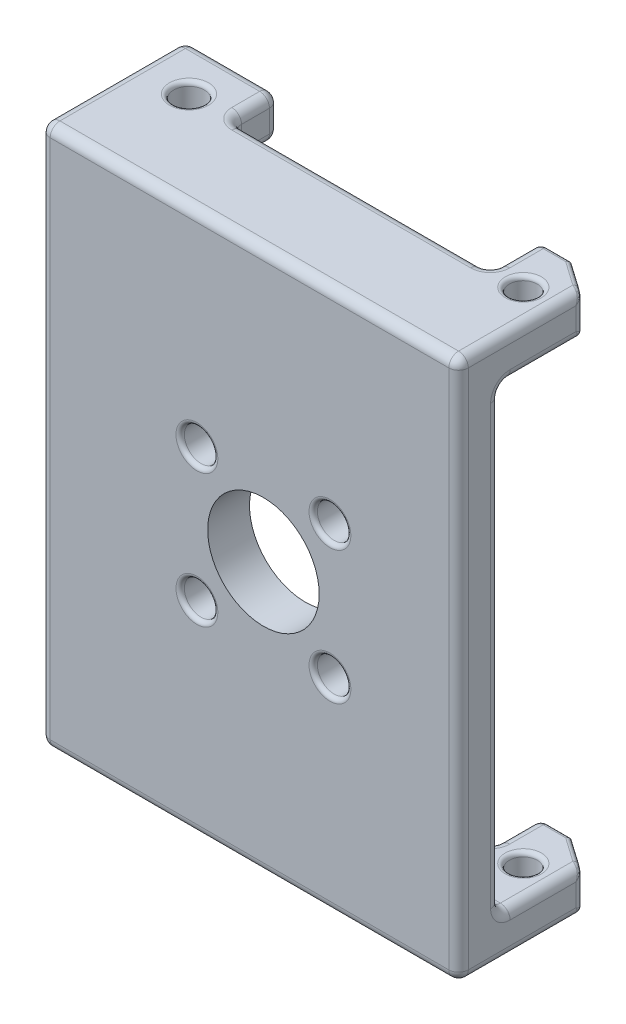
SolidWorks part; units mm, degrees
ref_plane "Front Plane" through (0, 0, 0) normal (0, 0, 1) x (1, 0, 0)
ref_plane "Top Plane" through (0, 0, 0) normal (0, 1, 0) x (1, 0, 0)
ref_plane "Right Plane" through (0, 0, 0) normal (1, 0, 0) x (0, 0, -1)
sketch "Sketch1" plane through (0, 0, 0) normal (0, 0, 1) x (1, 0, 0)
  line L1 (-14, -19.4) -> (14, -19.4)
  line L2 (-14, -19.4) -> (-14, 19.4)
  line L3 (-14, 19.4) -> (14, 19.4)
  line L4 (14, -19.4) -> (14, 19.4)
  line L5 (-14, -19.4) -> (14, 19.4) construction
  line L6 (-14, 19.4) -> (14, -19.4) construction
  circle A0 centre (0, 0) radius 4
  circle A1 centre (4.773, 4.773) radius 1.2
  circle A2 centre (4.773, -4.773) radius 1.2
  circle A3 centre (-4.773, -4.773) radius 1.2
  circle A4 centre (-4.773, 4.773) radius 1.2
  point P0 (0, 0)
  dimension "D1" = 14
  dimension "D4" = 2.4
  dimension "D5" = 8
  dimension "D7" = 2.4
  dimension "D11" = 2.4
  dimension "D15" = 2.4
  dimension "D2" = 19.4
  dimension "D3" = 6.75
  dimension "D6" = 4.773
  dimension "D8" = 6.75
  dimension "D9" = 4.773
  dimension "D10" = 6.75
  dimension "D12" = 4.773
  dimension "D13" = 6.75
  dimension "D14" = 4.773
extrude "Boss-Extrude1" add sketch "Sketch1" along normal blind 3
sketch "Sketch2" plane through (0, 19.4, 0) normal (0, 1, 0) x (1, 0, 0)
  line L1 (-14, 7.4) -> (-9.27, 7.4)
  line L2 (-9.27, 7.4) -> (-9.27, 4)
  line L3 (-9.27, 4) -> (9.27, 4)
  line L4 (9.27, 7.4) -> (9.27, 4)
  line L5 (9.27, 7.4) -> (11.68, 7.4)
  line L6 (14, -3) -> (14, 5.7755)
  line L8 (-14, -3) -> (14, -3)
  line L9 (-14, -3) -> (-14, 7.4)
  line L10 (11.68, 7.4) -> (14, 5.7755)
  line L12 (14, 0) -> (-14, 0) construction
  circle A3 centre (-12.34, 4) radius 1.1
  arc A7 (12.66, 3.986) -> (10.66, 3.986) centre (11.66, 3.986) ccw
  arc A8 (10.66, 3.986) -> (12.66, 3.986) centre (11.66, 3.986) ccw
  arc A9 (12.66, 3.986) -> (10.66, 3.986) centre (11.66, 3.986) ccw
  arc A10 (10.66, 3.986) -> (12.66, 3.986) centre (11.66, 3.986) ccw
  dimension "D1" = 0
  dimension "D11" = 2.2
  dimension "D2" = 24
  dimension "D3" = 28
  dimension "D4" = 4
  dimension "D5" = 7.4
  dimension "D6" = 7.4
  dimension "D7" = 125
  dimension "D8" = 2.8322
  dimension "D9" = 4.73
  dimension "D10" = 4.73
  dimension "D12" = 4
extrude "Boss-Extrude2" add sketch "Sketch2" against normal blind 3
sketch "Sketch3" plane through (0, -19.4, 0) normal (0, -1, 0) x (1, 0, 0)
  line L0 (-14, 0) -> (14, 0) construction
  line L1 (-14, 3) -> (14, 3) construction
  line L3 (9.27, -7.4) -> (9.27, -4) construction
  line L4 (11.68, -7.4) -> (9.27, -7.4) construction
  line L5 (14, -5.7755) -> (11.68, -7.4) construction
  line L9 (-9.27, -4) -> (-9.27, -7.4) construction
  line L10 (9.27, -4) -> (-9.27, -4) construction
  line L12 (-14, 3) -> (14, 3)
  line L14 (9.27, -7.4) -> (9.27, -4)
  line L15 (11.68, -7.4) -> (9.27, -7.4)
  line L16 (14, -5.7755) -> (11.68, -7.4)
  line L21 (9.27, -4) -> (-5.44, -4)
  line L22 (-14, -7.4) -> (-5.44, -7.4)
  line L23 (-5.44, -7.4) -> (-5.44, -4)
  line L24 (-14, 3) -> (-14, -7.4)
  line L25 (14, 3) -> (14, -5.7755)
  circle A3 centre (11.66, -3.986) radius 1 construction
  circle A5 centre (11.66, -3.986) radius 1
  circle A7 centre (-8.34, -4) radius 1.1
  dimension "D1" = 20
  dimension "D3" = 2.2
  dimension "D2" = 4
  dimension "D4" = 8.56
extrude "Boss-Extrude3" add sketch "Sketch3" against normal blind 3
sketch "草图3" plane through (-14, 0, 0) normal (-1, 0, 0) x (0, 0, 1)
  line L0 (-7.4, 19.4) -> (-7.4, 16.4)
  line L1 (-7.4, 16.4) -> (0, 16.4)
  line L2 (0, 16.4) -> (0, -16.4)
  line L3 (0, -16.4) -> (-7.4, -16.4)
  line L4 (-7.4, -16.4) -> (-7.4, -19.4)
  line L5 (-7.4, -19.4) -> (3, -19.4)
  line L6 (3, -19.4) -> (3, 19.4)
  line L7 (3, 19.4) -> (-7.4, 19.4)
extrude "凸台-拉伸1" add sketch "草图3" along normal blind 2
fillet "圆角1" radius 0.7 43 edges at (-5.44, -16.4, -5.7) (-5.44, -17.9, -4) (-9.27, 17.9, -4) (0, 19.4, -4) (-9.27, 19.4, -5.7) (14, 16.4, -2.8878) (14, 19.4, -1.3878) (14, 0, 0) (14, -16.4, -2.8878) (14, -19.4, -1.3878) (9.27, -17.9, -7.4) (-5.44, -17.9, -7.4) (-10.72, -16.4, -7.4) (-10.72, -19.4, -7.4) (-5.44, -19.4, -5.7) (1.915, -19.4, -4) (1.915, -16.4, -4) (9.27, -17.9, -4) (9.27, -19.4, -5.7) (9.27, -16.4, -5.7) (9.27, 19.4, -5.7) (9.27, 17.9, -4) (9.27, 16.4, -5.7) (-9.27, 16.4, -5.7) (0, 16.4, -4) (-9.27, 17.9, -7.4) (-12.635, 19.4, -7.4) (-16, 17.9, -7.4) (-12.635, 16.4, -7.4) (-1, 16.4, 0) (-1, -19.4, 3) (-16, -19.4, -2.2) (-16, -17.9, -7.4) (-16, -16.4, -3.7) (-16, 0, 0) (-16, 16.4, -3.7) (-16, 19.4, -2.2) (-16, 0, 3) (14, 0, 3) (-1, 19.4, 3) (14, 17.9, -5.7755) (14, -17.9, -5.7755) (-1, -16.4, 0)
fillet "圆角2" radius 0.3 36 edges at (-8.34, -16.4, -5.1) (-12.34, 19.4, -2.9) (11.66, 19.4, -2.986) (11.66, -16.4, -4.986) (11.66, -19.4, -4.986) (-8.34, -19.4, -5.1) (-12.34, 16.4, -2.9) (5.973, 4.773, 0) (3.573, -4.773, 0) (-3.573, -4.773, 0) (-5.973, 4.773, 0) (-3.573, -4.773, 3) (3.573, -4.773, 3) (5.973, 4.773, 3) (-5.973, 4.773, 3) (9.475, -16.605, -7.195) (9.475, -19.195, -7.195) (13.5105, -19.3676, -6.1183) (13.9209, -19.0232, -5.7343) (13.9209, -16.7768, -5.7343) (13.5105, -16.4324, -6.1183) (13.5105, 16.4324, -6.1183) (13.9209, 16.7768, -5.7343) (13.9209, 19.0232, -5.7343) (13.5105, 19.3676, -6.1183) (9.475, 19.195, -7.4) (9.27, 17.9, -7.4) (9.475, 16.605, -7.4) (10.825, 16.4, -7.4) (10.825, 19.4, -7.4) (10.825, -19.4, -7.4) (12.49, -19.4, -6.8328) (10.825, -16.4, -7.4) (12.49, -16.4, -6.8328) (12.49, 16.4, -6.8328) (12.49, 19.4, -6.8328)
